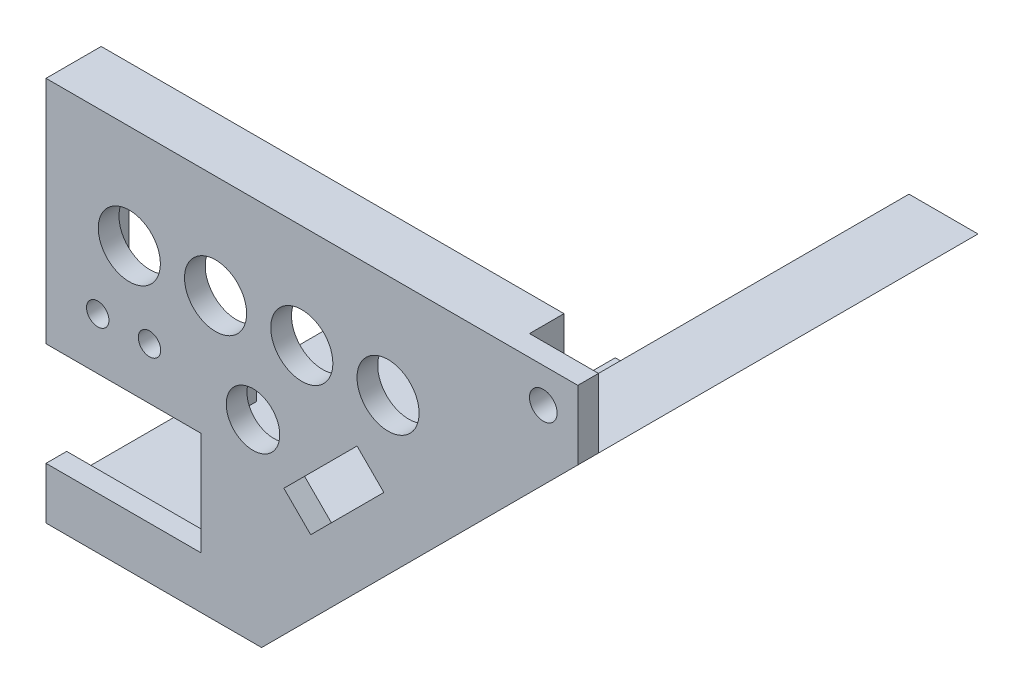
SolidWorks part; units mm, degrees
ref_plane "Plan de face" through (0, 0, 0) normal (0, 0, 1) x (1, 0, 0)
ref_plane "Plan de dessus" through (0, 0, 0) normal (0, 1, 0) x (1, 0, 0)
ref_plane "Plan de droite" through (0, 0, 0) normal (1, 0, 0) x (0, 0, -1)
sketch "Main-Sketch" plane through (0, 0, 0) normal (0, 0, 1) x (1, 0, 0)
  line L0 (0, 0) -> (62.5, 0)
  line L1 (62.5, 0) -> (154.15, 91.65)
  line L2 (154.15, 91.65) -> (154.15, 111.65)
  line L3 (0, 111.65) -> (0, 0)
  line L4 (154.15, 111.65) -> (0, 111.65)
  dimension "D1" = 135
  dimension "D2" = 154.15
  dimension "D3" = 62.5
  dimension "D4" = 20
  dimension "D5" = 129.6127
extrude "Main-Extrusion" add sketch "Main-Sketch" along normal blind 6
sketch "MainHole-Sketch" plane through (0, 0, 6) normal (0, 0, 1) x (1, 0, 0)
  line L0 (0, 0) -> (62.5, 0) construction
  line L2 (154.15, 91.65) -> (154.15, 111.65) construction
  line L3 (68.9454, 43.215) -> (76.7236, 35.4368)
  line L4 (76.7236, 35.4368) -> (97.9368, 56.65)
  line L5 (97.9368, 56.65) -> (90.1586, 64.4282)
  line L6 (90.1586, 64.4282) -> (68.9454, 43.215)
  line L7 (62.5, 0) -> (154.15, 91.65) construction
  line L9 (154.15, 111.65) -> (0, 111.65) construction
  line L10 (0, 111.65) -> (0, 0) construction
  line L11 (0, 111.65) -> (0, 0) construction
  circle A0 centre (49.15, 81.65) radius 9
  circle A1 centre (74.15, 81.65) radius 9
  circle A2 centre (99.15, 81.65) radius 9
  circle A3 centre (24.15, 81.65) radius 9
  circle A4 centre (60, 56) radius 7.75
  circle A5 centre (30, 60) radius 3.25
  circle A6 centre (15, 60) radius 3.25
  point P14 (154.15, 101.65)
  dimension "D1" = 18
  dimension "D4" = 25
  dimension "D11" = 15.5
  dimension "D5" = 6.5
  dimension "D2" = 25
  dimension "D3" = 25
  dimension "D6" = 55
  dimension "D7" = 11
  dimension "D8" = 30
  dimension "D9" = 15
  dimension "D10" = 55
  dimension "D12" = 56
  dimension "D13" = 60
  dimension "D14" = 30
  dimension "D15" = 30
  dimension "D16" = 60
  dimension "D17" = 15
extrude "MainHole" cut sketch "MainHole-Sketch" against normal through all
sketch "Vertical-Fix-Hole-Sketch" plane through (0, 0, 6) normal (0, 0, 1) x (1, 0, 0)
  line L0 (154.15, 91.65) -> (154.15, 111.65) construction
  line L1 (154.15, 111.65) -> (0, 111.65) construction
  circle A0 centre (144.15, 101.65) radius 4
  dimension "D3" = 8
  dimension "D1" = 10
  dimension "D2" = 10
extrude "Vertical-Fix-Hole" cut sketch "Vertical-Fix-Hole-Sketch" against normal through all
sketch "MotherBoard-Vertical-Hole-Sketch" plane through (0, 0, 6) normal (0, 0, 1) x (1, 0, 0)
  line L0 (0, 111.65) -> (0, 0) construction
  line L1 (0, 45) -> (45, 45)
  line L2 (0, 45) -> (0, 15)
  line L3 (0, 15) -> (45, 15)
  line L4 (45, 45) -> (45, 15)
  line L5 (0, 0) -> (62.5, 0) construction
  dimension "D1" = 45
  dimension "D2" = 45
  dimension "D3" = 30
extrude "MotherBoard-Vertical-Hole" cut sketch "MotherBoard-Vertical-Hole-Sketch" against normal through all
sketch "Front-Vertical-Sketch" plane through (0, 0, 0) normal (0, 0, -1) x (-1, 0, 0)
  line L0 (-154.15, 91.65) -> (-134.15, 91.65)
  line L1 (-138.4931, 87.3069) -> (-59.1863, 8)
  line L2 (-59.1863, 8) -> (0, 8)
  line L3 (0, 15) -> (0, 0) construction
  line L4 (0, 8) -> (0, 0)
  line L5 (0, 0) -> (-62.5, 0)
  line L6 (-62.5, 0) -> (-154.15, 91.65) construction
  line L7 (0, 0) -> (-62.5, 0) construction
  line L8 (-62.5, 0) -> (-154.15, 91.65)
  line L9 (-134.15, 91.65) -> (-138.4931, 87.3069)
  dimension "D1" = 8
  dimension "D2" = 8
  dimension "D3" = 20
extrude "Front-Vertical-Extrusion" add sketch "Front-Vertical-Sketch" along normal blind 110
sketch "Reinforcement-Sketch" plane through (0, 0, 0) normal (0, 0, -1) x (-1, 0, 0)
  line L0 (-8, 51) -> (-45, 51)
  line L1 (-138.4931, 87.3069) -> (-134.15, 91.65) construction
  line L2 (-8, 51) -> (-8, 105.65)
  line L3 (-8, 105.65) -> (-128.15, 105.65)
  line L4 (-134.15, 111.65) -> (0, 111.65)
  line L5 (-154.15, 111.65) -> (0, 111.65) construction
  line L6 (0, 111.65) -> (0, 45)
  line L7 (-128.15, 76.9637) -> (-138.4931, 87.3069)
  line L8 (-59.1863, 8) -> (-138.4931, 87.3069) construction
  line L9 (-59.1863, 8) -> (-138.4931, 87.3069) construction
  line L10 (-138.4931, 87.3069) -> (-134.15, 91.65)
  line L11 (-128.15, 105.65) -> (-128.15, 76.9637)
  line L13 (-134.15, 91.65) -> (-134.15, 111.65)
  line L14 (-45, 51) -> (-45, 45)
  line L15 (-45, 45) -> (0, 45)
  line L16 (-45, 15) -> (-45, 45) construction
  dimension "D1" = 6
  dimension "D2" = 8
  dimension "D4" = 6
  dimension "D5" = 6
extrude "Reinforcement-Extrusion" add sketch "Reinforcement-Sketch" along normal blind 10
sketch "Right-Screw-Sketch" plane through (0, 0, 0) normal (-1, 0, 0) x (0, 0, 1)
  line L0 (-10, 45) -> (-10, 111.65) construction
  line L1 (6, 111.65) -> (-10, 111.65) construction
  circle A0 centre (-5, 101.65) radius 1.35
  dimension "D1" = 2.7
  dimension "D2" = 5
  dimension "D3" = 10
extrude "Right-Screw-Hole" cut sketch "Right-Screw-Sketch" against normal up to next
pattern_linear "Screw-Linear-Repetition" count 3 spacing 20 along (0, -1, 0) of "Right-Screw-Hole"
sketch "Right-Fix-Sketch" plane through (0, 0, 0) normal (-1, 0, 0) x (0, 0, 1)
  line L0 (6, 111.65) -> (-10, 111.65) construction
  line L1 (6, 111.65) -> (6, 45) construction
  line L2 (6, 0) -> (-110, 0) construction
  line L4 (0, 15) -> (0, 8) construction
  circle A0 centre (0, 91.65) radius 3
  circle A1 centre (0, 71.65) radius 3
  circle A2 centre (0, 51.65) radius 3
  circle A3 centre (-40, 4) radius 3
  circle A4 centre (0, 4) radius 3
  circle A5 centre (-80, 4) radius 3
  dimension "D2" = 6
  dimension "D8" = 40
  dimension "D1" = 20
  dimension "D3" = 20
  dimension "D4" = 20
  dimension "D5" = 6
  dimension "D6" = 4
  dimension "D7" = 40
extrude "Right-Fix-Extrusion" cut sketch "Right-Fix-Sketch" against normal up to surface (8 mm away) up to face at (8, 81.65, -3.65)
sketch "LcdHole-Sketch" plane through (0, 0, 0) normal (0, -1, 0) x (1, 0, 0)
  line L0 (0, 6) -> (62.5, 6) construction
  line L1 (0, -110) -> (49, -110)
  line L2 (0, -110) -> (0, -89)
  line L3 (0, -89) -> (49, -89)
  line L4 (49, -110) -> (49, -89)
  dimension "D1" = 95
  dimension "D2" = 49
extrude "LcdHole" cut sketch "LcdHole-Sketch" against normal through all
sketch "Lcd-Fix-Sketch" plane through (0, 8, 0) normal (0, -1, 0) x (-1, 0, 0)
  line L0 (-49, 110) -> (-49, 89) construction
  line L4 (-49, 89) -> (0, 89) construction
  circle A0 centre (-46.5, 83) radius 1.35
  dimension "D3" = 2.5
  dimension "D1" = 2.7
  dimension "D2" = 6
extrude "Lcd-Fix" cut sketch "Lcd-Fix-Sketch" along normal blind 7
hole_wizard "Fraisage pour vis à tête fraisée M32" positions "Esquisse3" profile "Esquisse4" countersink size "M3" standard "Ansi Metric" end condition up to next
sketch "Esquisse3" plane through (0, 0, 0) normal (0, -1, 0) x (-1, 0, 0)
  line L0 (0, -6) -> (-62.5, -6) construction
  line L1 (0, -6) -> (0, 89) construction
  point P0 (-52, 72)
  dimension "D1" = 78
  dimension "D2" = 52
sketch "Esquisse4" plane through (52, 0, -72) normal (1, 0, 0) x (0, 0, -1)
  line L0 (0, 0) -> (0, 8)
  line L1 (0, 8) -> (1.7, 8)
  line L2 (1.7, 8) -> (1.7, 1.45)
  line L3 (1.7, 1.45) -> (3.15, 0)
  line L5 (3.15, 0) -> (0, 0)
  line L6 (-1.7, 1.45) -> (-3.15, 0) construction
  line L11 (0, -6.35) -> (0, 107.95) construction
  dimension "Diamètre du perçage jusqu'au prochain" = 3.4
  dimension "Profondeur du perçage jusqu'au prochain" = 8
  dimension "Diamètre du fraisage entrant" = 6.3
  dimension "Angle du fraisage entrant" = 90
pattern_linear "MotherBoard-Fix-Linear-Repetition" count 2 spacing 66 along (0, 0, 1) of "Fraisage pour vis à tête fraisée M32"
sketch "PowerBoard-Hole-Sketch" plane through (31.25, -31.25, 0) normal (0.7071, -0.7071, 0) x (0, 0, -1)
  line L0 (110, 173.8068) -> (110, 44.1942) construction
  line L1 (37, 67.1942) -> (95, 67.1942)
  line L2 (37, 67.1942) -> (37, 141.8068)
  line L3 (37, 141.8068) -> (95, 141.8068)
  line L4 (95, 67.1942) -> (95, 141.8068)
  line L5 (-6, 44.1942) -> (-6, 173.8068) construction
  line L6 (-6, 44.1942) -> (110, 44.1942) construction
  line L8 (110, 173.8068) -> (0, 173.8068) construction
  dimension "D1" = 15
  dimension "D2" = 43
  dimension "D3" = 23
  dimension "D4" = 32
extrude "PowerBoard-Hole" cut sketch "PowerBoard-Hole-Sketch" against normal up to next
sketch "PowerBoard-Window-Sketch" plane through (31.25, -31.25, 0) normal (0.7071, -0.7071, 0) x (0, 0, -1)
  line L0 (37, 141.8068) -> (37, 67.1942) construction
  line L1 (31, 61.1942) -> (101, 61.1942)
  line L2 (31, 61.1942) -> (31, 147.8068)
  line L3 (31, 147.8068) -> (101, 147.8068)
  line L4 (101, 61.1942) -> (101, 147.8068)
  line L5 (37, 67.1942) -> (95, 67.1942) construction
  line L6 (95, 67.1942) -> (95, 141.8068) construction
  line L7 (95, 141.8068) -> (37, 141.8068) construction
  dimension "D1" = 6
  dimension "D2" = 6
  dimension "D3" = 6
  dimension "D4" = 6
extrude "PowerBoard-Window" cut sketch "PowerBoard-Window-Sketch" against normal blind 5
sketch "PowerBoard-Window-Fix-Sketch" plane through (27.7145, -27.7145, 0) normal (0.7071, -0.7071, 0) x (0, 0, -1)
  line L0 (31, 147.8068) -> (31, 61.1942) construction
  line L1 (37, 141.8068) -> (37, 67.1942) construction
  line L3 (31, 61.1942) -> (101, 61.1942) construction
  line L4 (37, 67.1942) -> (95, 67.1942) construction
  line L6 (95, 67.1942) -> (95, 141.8068) construction
  line L7 (95, 141.8068) -> (37, 141.8068) construction
  circle A0 centre (34, 104.5005) radius 1.25
  circle A1 centre (66, 64.1942) radius 1.25
  circle A2 centre (98, 104.5005) radius 1.25
  circle A3 centre (66, 144.8068) radius 1.25
  point P10 (31, 104.5005)
  point P13 (37, 104.5005)
  point P18 (66, 61.1942)
  point P19 (66, 67.1942)
  dimension "D1" = 2.5
  dimension "D2" = 3
  dimension "D3" = 3
  dimension "D4" = 3
  dimension "D5" = 3
extrude "PowerBoard-Window-Fix" cut sketch "PowerBoard-Window-Fix-Sketch" against normal through all
sketch "PowerBoard-Fix-Sketch" plane through (25.5931, -25.5931, 0) normal (-0.7071, 0.7071, 0) x (0, 0, 1)
  line L0 (-110, 159.6647) -> (-10, 159.6647) construction
  line L1 (0, 47.5079) -> (0, 145.0373) construction
  circle A0 centre (-32, 137.6647) radius 4
  circle A1 centre (-31, 69.1647) radius 3
  dimension "D1" = 8
  dimension "D2" = 6
  dimension "D3" = 68.5
  dimension "D4" = 1
  dimension "D5" = 22
  dimension "D6" = 32
extrude "PowerBoard-Fix" add sketch "PowerBoard-Fix-Sketch" along normal blind 5
sketch "PowerBoard-Fix-Hole-Sketch" plane through (22.0576, -22.0576, 0) normal (-0.7071, 0.7071, 0) x (0, 0, 1)
  circle A0 centre (-32, 137.6647) radius 1.25
  circle A1 centre (-31, 69.1647) radius 1.25
  dimension "D1" = 2.5
  dimension "D2" = 2.5
extrude "PowerBoard-Fix-Hole" cut sketch "PowerBoard-Fix-Hole-Sketch" against normal blind 7
sketch "Esquisse5" plane through (0, 0, -110) normal (0, 0, -1) x (-1, 0, 0)
  line L0 (-138.4931, 87.3069) -> (-134.15, 91.65)
  line L1 (-138.4931, 87.3069) -> (-134.15, 91.65) construction
  line L2 (-59.1863, 8) -> (-138.4931, 87.3069) construction
  line L3 (-134.15, 91.65) -> (-127.0789, 84.5789)
  line L4 (-127.0789, 84.5789) -> (-131.4221, 80.2358)
  line L5 (-131.4221, 80.2358) -> (-138.4931, 87.3069)
  dimension "D1" = 10
extrude "Boss.-Extru.1" add sketch "Esquisse5" against normal blind 10
sketch "Esquisse6" plane through (0, 0, -110) normal (0, 0, -1) x (-1, 0, 0)
  line L0 (-131.4221, 80.2358) -> (-127.0789, 84.5789) construction
  line L2 (-127.0789, 84.5789) -> (-134.15, 91.65) construction
  circle A0 centre (-132.7853, 85.9436) radius 1.35
  dimension "D1" = 2.7
  dimension "D2" = 5
  dimension "D3" = 3.07
extrude "Enlèv. mat.-Extru.1" cut sketch "Esquisse6" against normal up to next
